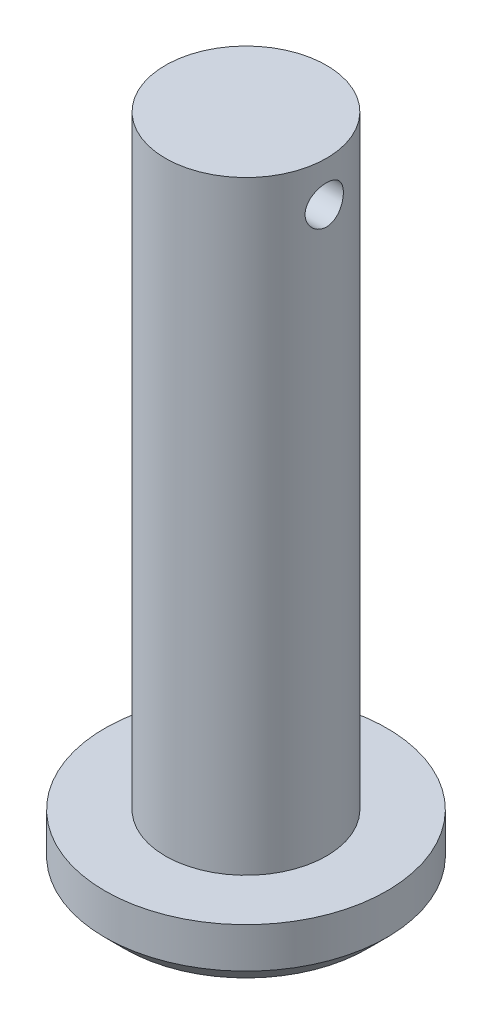
SolidWorks part; units mm, degrees
ref_plane "Front Plane" through (0, 0, 0) normal (0, 0, 1) x (1, 0, 0)
ref_plane "Top Plane" through (0, 0, 0) normal (0, 1, 0) x (1, 0, 0)
ref_plane "Right Plane" through (0, 0, 0) normal (1, 0, 0) x (0, 0, -1)
sketch "Sketch1" plane through (0, 0, 0) normal (0, 1, 0) x (1, 0, 0)
  circle A0 centre (0, 0) radius 7
  circle A1 centre (0, 0) radius 4
  dimension "D1" = 14
  dimension "D2" = 8
extrude "Boss-Extrude1" add sketch "Sketch1" against normal blind 3 contours A0
extrude "Boss-Extrude2" add sketch "Sketch1<3>" along normal blind 30 contours A1
sketch "Sketch1<3>" plane through (0, 0, 0) normal (0, 1, 0) x (1, 0, 0) same geometry as "Sketch1"
chamfer "Chamfer1" distance 1 angle 45 1 edges at (0, -3, 7)
ref_plane "Plane1" through (-4, 0, 0) normal (-1, 0, 0) x (0, 0, 1)
sketch "Sketch2" plane through (-4, 0, 0) normal (-1, 0, 0) x (0, 0, 1)
  line L0 (4, 30) -> (-4, 30) construction
  circle A0 centre (0, 28) radius 0.95
  dimension "D1" = 1.9
  dimension "D2" = 2
extrude "Cut-Extrude1" cut sketch "Sketch2" against normal up to next contours A0
